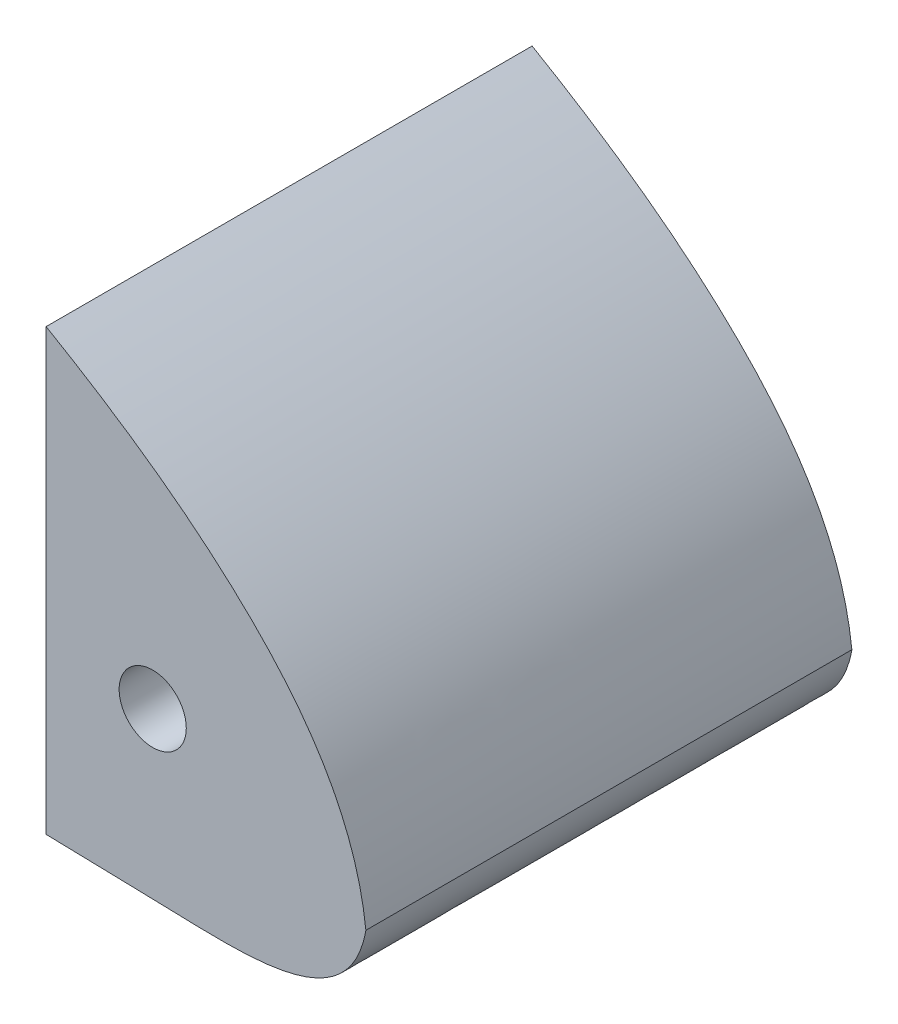
SolidWorks part; units mm, degrees
ref_plane "Front Plane" through (0, 0, 0) normal (0, 0, 1) x (1, 0, 0)
ref_plane "Top Plane" through (0, 0, 0) normal (0, 1, 0) x (1, 0, 0)
ref_plane "Right Plane" through (0, 0, 0) normal (1, 0, 0) x (0, 0, -1)
sketch "Sketch1" plane through (0, 0, 0) normal (0, 0, 1) x (1, 0, 0)
  line L0 (-66.007, 14.9523) -> (-66.007, -5.6347)
  circle A0 centre (63.517, -7.2283) radius 2
  circle A1 centre (-25.383, 13.0917) radius 2.127
  spline S0 degree 3 poles (76.217, -12.3083) (75.607, -6.7666) (69.7043, 1.1384) (56.4222, 10.2644) (36.9761, 19.3708) (8.7417, 24.8154) (-27.4552, 23.5667) (-52.3876, 18.1036) (-66.007, 14.9523) knots 0 0 0 0 0.086587 0.161737 0.268322 0.445157 0.638029 0.872371 0.872371 0.872371 0.872371
  spline S1 degree 3 poles (-66.007, -5.6347) (-44.594, -5.5392) (-13.013, -6.7241) (26.1367, -12.7509) (48.7653, -16.9008) (64.6834, -16.9691) (75.2906, -17.5225) (76.217, -12.3083) knots 0.133251 0.133251 0.133251 0.133251 0.51733 0.696667 0.84941 0.91952 1 1 1 1
  dimension "D2" = 4
  dimension "D1" = 142.224
extrude "Boss-Extrude1" add sketch "Sketch1" along normal blind 28.956
sketch "Sketch2" plane through (0, 0, 28.956) normal (0, 0, 1) x (1, 0, 0)
  line L0 (-66.007, 14.9523) -> (-66.007, -5.6347) construction
  line L1 (-77.1256, 30.6925) -> (57.167, 30.6925)
  line L2 (-77.1256, 30.6925) -> (-77.1256, -22.6703)
  line L3 (-77.1256, -22.6703) -> (57.167, -22.6703)
  line L4 (57.167, 30.6925) -> (57.167, -22.6703)
  dimension "D1" = 11.1187
  dimension "D2" = 19.05
extrude "Cut-Extrude1" cut sketch "Sketch2" against normal blind 28.956
